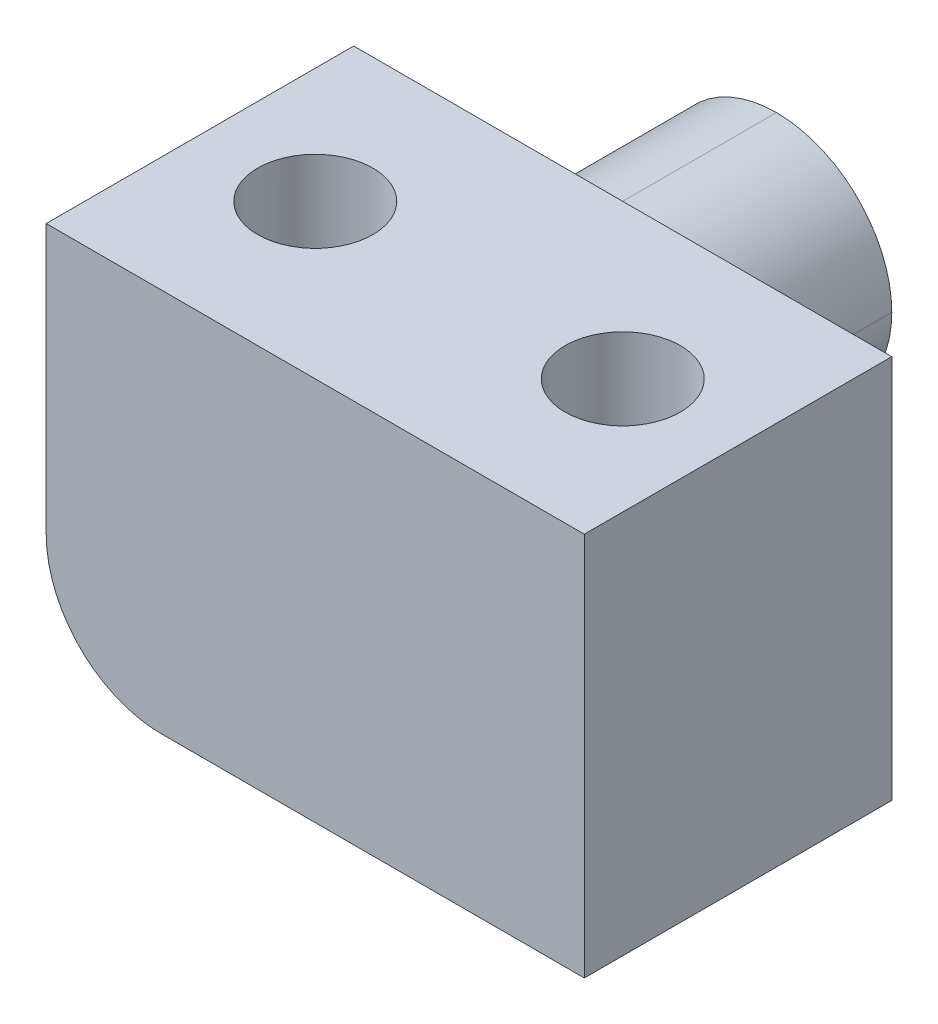
SolidWorks part; units mm, degrees
ref_plane "Front Plane" through (0, 0, 0) normal (0, 0, 1) x (1, 0, 0)
ref_plane "Top Plane" through (0, 0, 0) normal (0, 1, 0) x (1, 0, 0)
ref_plane "Right Plane" through (0, 0, 0) normal (1, 0, 0) x (0, 0, -1)
sketch "Sketch1" plane through (0, 0, 0) normal (0, 1, 0) x (1, 0, 0)
  line L1 (1.5, -4) -> (-1.5, -4)
  line L2 (1.5, -4) -> (1.5, 4)
  line L3 (1.5, 4) -> (-1.5, 4)
  line L4 (-1.5, -4) -> (-1.5, 4)
  line L5 (1.5, -4) -> (-1.5, 4) construction
  line L6 (1.5, 4) -> (-1.5, -4) construction
  point P0 (0, 0)
  dimension "D1" = 3
  dimension "D2" = 8
extrude "Boss-Extrude1" add sketch "Sketch1" along normal blind 3
sketch "Sketch2" plane through (1.5, 0, 0) normal (1, 0, 0) x (0, 0, -1)
  line L0 (-4, 0) -> (4, 0) construction
  line L1 (-4, 3) -> (0, 3)
  line L2 (-4, 3) -> (-4, 0)
  line L3 (-4, 0) -> (0, 0)
  line L4 (0, 3) -> (0, 0)
  dimension "D1" = 4
extrude "Boss-Extrude2" add sketch "Sketch2" along normal blind 4
sketch "Sketch4" plane through (0, 3, 0) normal (0, -1, 0) x (-1, 0, 0)
  line L1 (1.5, -4) -> (-5.5, -4)
  line L2 (1.5, -4) -> (1.5, 0)
  line L3 (1.5, 0) -> (-5.5, 0)
  line L4 (-5.5, -4) -> (-5.5, 0)
extrude "Boss-Extrude3" add sketch "Sketch4" against normal blind 2
sketch "Sketch5" plane through (0, 5, 0) normal (0, 1, 0) x (1, 0, 0)
  line L0 (5.5, 0) -> (5.5, -4) construction
  circle A0 centre (0, -2) radius 0.75
  circle A1 centre (4, -2) radius 0.75
  point P4 (0, 0)
  point P8 (5.5, -2)
  dimension "D2" = 1.5
  dimension "D3" = 1.5
  dimension "D1" = 4
extrude "Cut-Extrude2" cut sketch "Sketch5" against normal up to next
fillet "Fillet4" radius 1.5 4 edges at (1.5, 0, -2) (1.5, 3, -2) (-1.5, 3, -2) (-1.5, 0, 0)
equation "\"D3@Sketch5\"=\"D2@Sketch5\""
